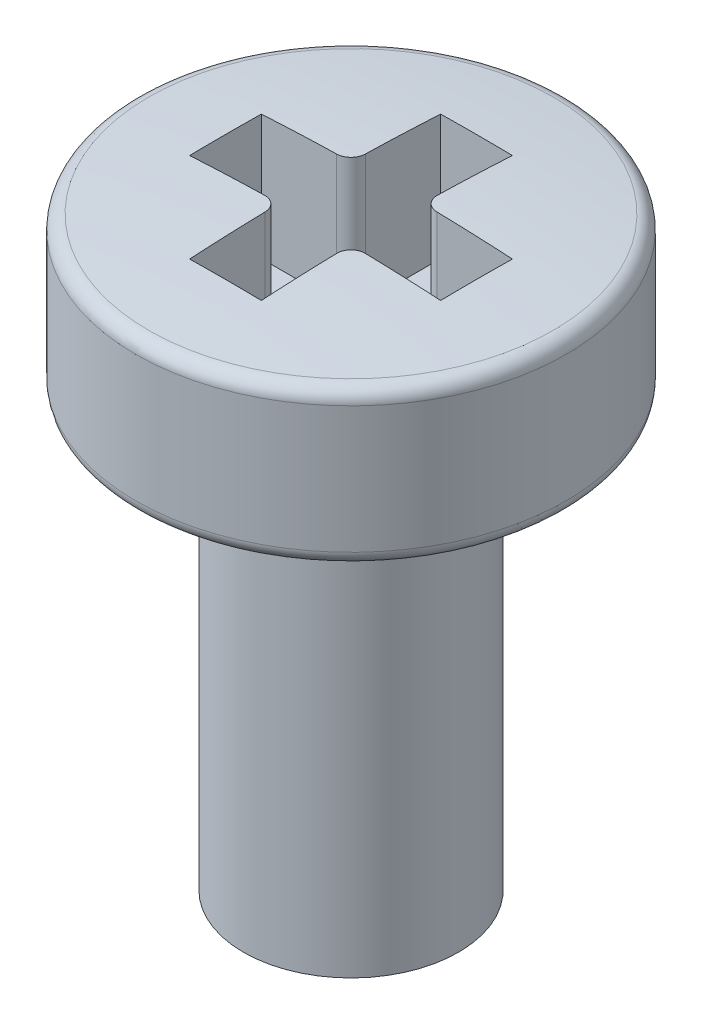
SolidWorks part; units mm, degrees
ref_plane "Alzado" through (0, 0, 0) normal (0, 0, 1) x (1, 0, 0)
ref_plane "Planta" through (0, 0, 0) normal (0, 1, 0) x (1, 0, 0)
ref_plane "Vista lateral" through (0, 0, 0) normal (1, 0, 0) x (0, 0, -1)
sketch "Croquis1" plane through (0, 0, 0) normal (0, 1, 0) x (1, 0, 0)
  circle A0 centre (0, 0) radius 1.5
  dimension "D1" = 3
extrude "Saliente-Extruir1" add sketch "Croquis1" along normal blind 6 contours A0
cosmetic thread "Cosmetic Thread1" parameters "D2"=2.439
sketch "Croquis2" plane through (0, 0, 0) normal (0, -1, 0) x (1, 0, 0)
  circle A0 centre (0, 0) radius 1.5 construction
  circle A1 centre (0, 0) radius 1.5
curve "Hélice/Espiral1" [suppressed] pitch 0.55 height 6.05 turns 11
sketch "Croquis3" plane through (0, 0, 0) normal (1, 0, 0) x (0, 0, -1)
  line L0 (1.5, 0.2) -> (1.5, -0.2)
  line L1 (1.5, 0) -> (1.5, 6) construction
  line L2 (1.5, -0.2) -> (1.25, 0)
  line L3 (-1.5, 0) -> (1.5, 0) construction
  line L4 (1.25, 0) -> (1.5, 0.2)
  dimension "D1" = 0.25
  dimension "D2" = 0.4
sweep "Cortar-Barrer3" [suppressed] cut profiles "Croquis3" path "Hélice/Espiral1"
sketch "Croquis4" plane through (0, 0, 0) normal (0, 0, 1) x (1, 0, 0)
  line L0 (1.5, 6) -> (-1.5, 6) construction
  line L1 (0, 6) -> (2.8, 6)
  line L2 (0, 6) -> (0, 8.3)
  line L3 (-1.3027, 8.3) -> (0, 8.3) construction
  line L4 (3, 6.2) -> (3, 7.9682)
  arc A0 (2.8188, 8.1673) -> (0, 8.3) centre (0, -21.7) ccw
  arc A1 (2.8188, 8.1673) -> (3, 7.9682) centre (2.8, 7.9682) cw
  arc A2 (2.8, 6) -> (3, 6.2) centre (2.8, 6.2) ccw
  point P4 (0, 6.4326)
  point P5 (0, 6)
  point P12 (3, 6)
  dimension "D2" = 0.2
  dimension "D4" = 30
  dimension "D1" = 3
  dimension "D3" = 2.3
revolve "Revolución1" add sketch "Croquis4" angle 360 about L2
ref_plane "Plano1" through (0, 9, 0) normal (0, 1, 0) x (1, 0, 0)
sketch "Croquis5" plane through (0, 9, 0) normal (0, 1, 0) x (1, 0, 0)
  line L0 (-0.5, -0.7) -> (-0.5, -1.75)
  line L1 (-0.5, 1.75) -> (0.5, 1.75)
  line L2 (-0.5, 1.75) -> (-0.5, 0.7)
  line L3 (-0.5, -1.75) -> (0.5, -1.75)
  line L4 (0.5, 1.75) -> (0.5, 0.7)
  line L5 (1.75, 0.5) -> (0.7, 0.5)
  line L6 (1.75, 0.5) -> (1.75, -0.5)
  line L7 (1.75, -0.5) -> (0.7, -0.5)
  line L8 (-1.75, 0.5) -> (-1.75, -0.5)
  line L9 (-0.7, 0.5) -> (-1.75, 0.5)
  line L10 (0.5, -0.7) -> (0.5, -1.75)
  line L11 (-0.7, -0.5) -> (-1.75, -0.5)
  line L12 (-1.75, 0) -> (1.75, 0) construction
  line L13 (0, 1.75) -> (0, -1.75) construction
  arc A0 (-0.5, -0.7) -> (-0.7, -0.5) centre (-0.7, -0.7) ccw
  arc A1 (0.5, -0.7) -> (0.7, -0.5) centre (0.7, -0.7) cw
  arc A2 (0.7, 0.5) -> (0.5, 0.7) centre (0.7, 0.7) cw
  arc A3 (-0.5, 0.7) -> (-0.7, 0.5) centre (-0.7, 0.7) cw
  point P19 (-0.5, -0.5)
  point P26 (-0.5, 0.5)
  dimension "D2" = 0.2
  dimension "D1" = 1
  dimension "D3" = 3.5
extrude "Cortar-Extruir1" cut sketch "Croquis5" against normal blind 2.5
